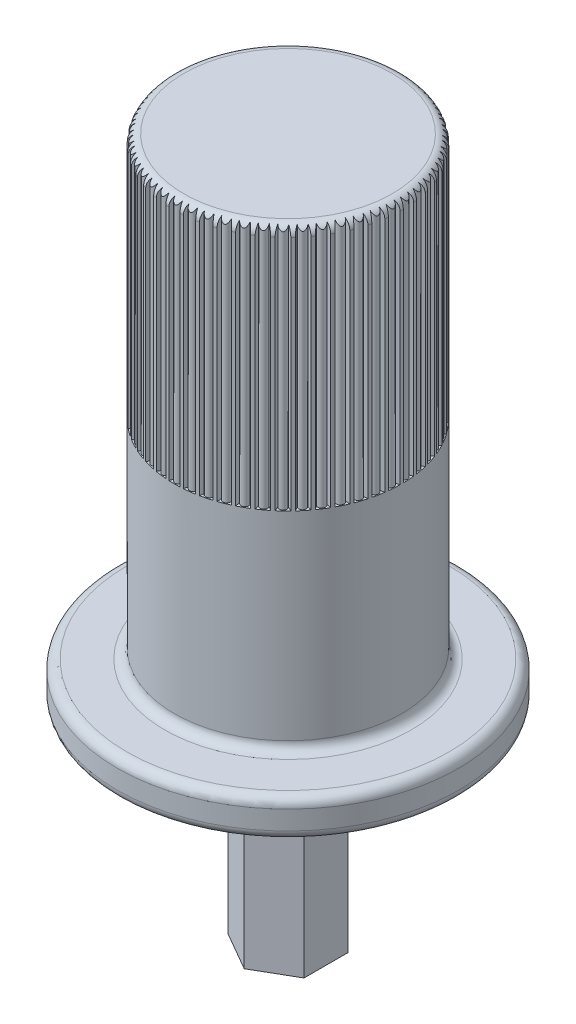
SolidWorks part; units mm, degrees
material "ABS"
ref_plane "Front" through (0, 0, 0) normal (0, 0, 1) x (1, 0, 0)
ref_plane "Top" through (0, 0, 0) normal (0, 1, 0) x (1, 0, 0)
ref_plane "Right" through (0, 0, 0) normal (1, 0, 0) x (0, 0, -1)
sketch "Sketch1" plane through (0, 0, 0) normal (0, 0, 1) x (1, 0, 0)
  line L0 (0, 0) -> (0, 13)
  line L1 (0, 13) -> (-3, 13)
  line L2 (-3, 13) -> (-3, 1)
  line L3 (-3, 1) -> (-4.5, 1)
  line L4 (-4.5, 1) -> (-4.5, 0)
  line L5 (-4.5, 0) -> (0, 0)
  dimension "D1" = 4.5
  dimension "D2" = 3
  dimension "D3" = 1
  dimension "D4" = 13
revolve "Revolve1" add sketch "Sketch1" angle 360 about L0
fillet "Fillet1" radius 0.25 1 edges at (0, 13, -3)
sketch "Sketch2" plane through (0, 13, 0) normal (0, 1, 0) x (1, 0, 0)
  line L0 (-0.1, 2.8733) -> (-0.25, 3.2733)
  line L1 (-0.25, 3.2733) -> (0.25, 3.2733)
  line L2 (0.25, 3.2733) -> (0.1, 2.8733)
  circle A0 centre (0, 0) radius 2.875 construction
  arc A1 (-0.1, 2.8733) -> (0.1, 2.8733) centre (0, 2.875) cw
  point P6 (0, 2.8724)
  dimension "D1" = 0.1
  dimension "D2" = 5.75
  dimension "D3" = 0.5
  dimension "D4" = 0.4
extrude "Cut-Extrude1" cut sketch "Sketch2" against normal blind 6.5
pattern_circular "CirPattern1" count 50 over 360 about axis through (0, 0, 0) along (0, -1, 0) of "Cut-Extrude1"
fillet "Fillet2" radius 0.25 3 edges at (0, 0, -4.5) (0, 1, -3) (0, 1, -4.5)
sketch "Sketch3" plane through (0, 0, 0) normal (0, 1, 0) x (1, 0, 0)
  line L1 (0, 1.1547) -> (-1, 0.5774)
  line L2 (-1, 0.5774) -> (-1, -0.5774)
  line L3 (-1, -0.5774) -> (0, -1.1547)
  line L4 (0, -1.1547) -> (1, -0.5774)
  line L5 (1, -0.5774) -> (1, 0.5774)
  line L6 (1, 0.5774) -> (0, 1.1547)
  circle A0 centre (0, 0) radius 1 construction
  point P1 (0.9659, 0.5202)
  dimension "D1" = 2
extrude "Boss-Extrude1" add sketch "Sketch3" against normal blind 5.5
